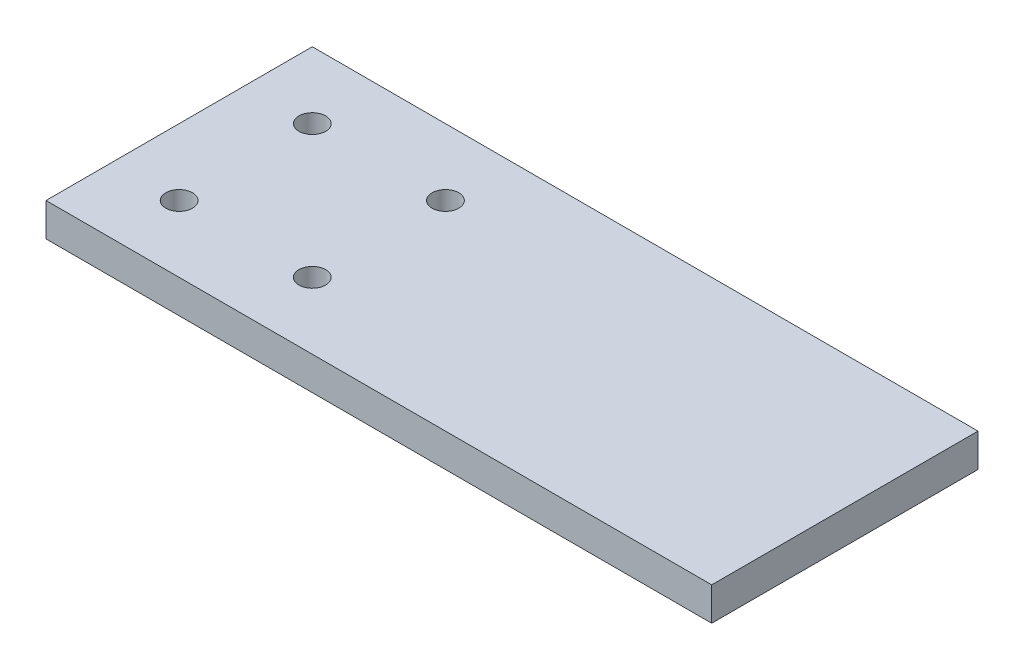
SolidWorks part; units mm, degrees
ref_plane "Front Plane" through (0, 0, 0) normal (0, 0, 1) x (1, 0, 0)
ref_plane "Top Plane" through (0, 0, 0) normal (0, 1, 0) x (1, 0, 0)
ref_plane "Right Plane" through (0, 0, 0) normal (1, 0, 0) x (0, 0, -1)
sketch "Sketch1" plane through (0, 0, 0) normal (0, 1, 0) x (1, 0, 0)
  line L0 (50.8, 25.4) -> (76.2, 25.4)
  line L1 (-50.8, -25.4) -> (50.8, -25.4)
  line L2 (-50.8, -25.4) -> (-50.8, 25.4)
  line L3 (-50.8, 25.4) -> (50.8, 25.4)
  line L5 (-50.8, -25.4) -> (50.8, 25.4) construction
  line L6 (-50.8, 25.4) -> (50.8, -25.4) construction
  line L7 (76.2, 25.4) -> (76.2, -25.4)
  line L8 (76.2, -25.4) -> (50.8, -25.4)
  point P0 (0, 0)
  dimension "D1" = 101.6
  dimension "D2" = 50.8
  dimension "D3" = 25.4
extrude "Boss-Extrude1" add sketch "Sketch1" along normal blind 6.35
sketch "Sketch2" plane through (0, 6.35, 0) normal (0, 1, 0) x (1, 0, 0)
  line L4 (76.2, 25.4) -> (-50.8, 25.4) construction
  line L5 (-50.8, -25.4) -> (76.2, -25.4) construction
  line L7 (0, 25.4) -> (0, -25.4) construction
  line L8 (-50.8, 25.4) -> (-50.8, -25.4) construction
  dimension "D1" = 50.8
hole_wizard "#10 Clearance Hole1" positions "Sketch3" profile "Sketch4" hole size "#10" standard "ANSI Inch" end condition through all
sketch "Sketch3" plane through (0, 6.35, 0) normal (0, 1, 0) x (1, 0, 0)
  line L4 (-38.1, 25.4) -> (-38.1, -25.4) construction
  line L5 (76.2, 25.4) -> (-50.8, 25.4) construction
  line L6 (-50.8, -25.4) -> (76.2, -25.4) construction
  line L8 (-12.7, 25.4) -> (-12.7, -25.4) construction
  line L9 (-50.8, 25.4) -> (-50.8, -25.4) construction
  line L11 (-50.8, 12.7) -> (0, 12.7) construction
  line L13 (-50.8, -12.7) -> (0, -12.7) construction
  point P0 (-38.1, 12.7)
  point P2 (-12.7, 12.7)
  point P4 (-12.7, -12.7)
  point P6 (-38.1, -12.7)
  dimension "D1" = 12.7
  dimension "D2" = 38.1
  dimension "D3" = 12.7
  dimension "D4" = 12.7
  dimension "D5" = 50.8
  dimension "D6" = 50.8
sketch "Sketch4" plane through (-38.1, 6.35, -12.7) normal (1, 0, 0) x (0, 0, 1)
  line L0 (0, 0) -> (0, 6.35)
  line L1 (0, 6.35) -> (2.5527, 6.35)
  line L2 (2.5527, 6.35) -> (2.5527, 0)
  line L5 (2.5527, 0) -> (0, 0)
  line L11 (0, -6.35) -> (0, 107.95) construction
  dimension "Thru Hole Dia." = 5.1054
  dimension "Thru Hole Depth" = 6.35
